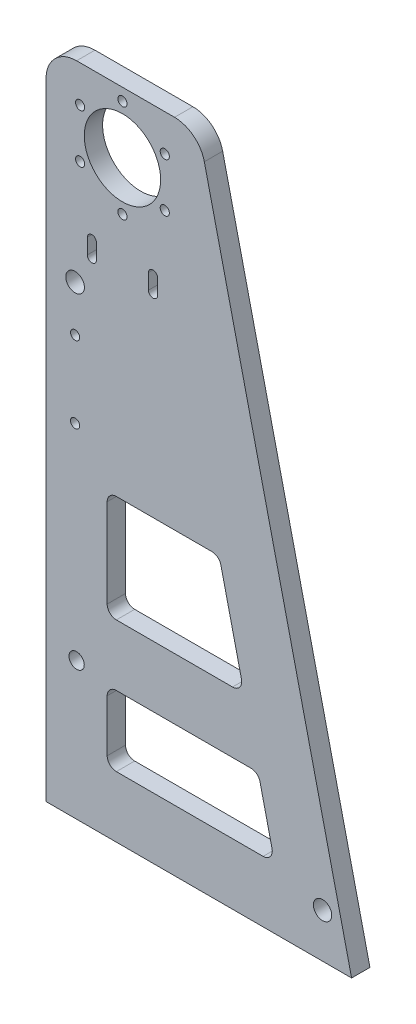
SolidWorks part; units mm, degrees
material "Policarbonato"
ref_plane "Plano frontal" through (0, 0, 0) normal (0, 0, 1) x (1, 0, 0)
ref_plane "Plano superior" through (0, 0, 0) normal (0, 1, 0) x (1, 0, 0)
ref_plane "Plano direito" through (0, 0, 0) normal (1, 0, 0) x (0, 0, -1)
sketch "Esboço1" plane through (0, 0, 0) normal (0, 0, 1) x (1, 0, 0)
  line L0 (0, 0) -> (0, 215)
  line L2 (100, 0) -> (0, 0)
  line L3 (0, 215) -> (50, 215)
  line L4 (50, 215) -> (100, 0)
  line L5 (10, 75.4302) -> (10, 15) construction
  line L6 (25, 215) -> (25, 175) construction
  line L7 (10, 15) -> (85.7122, 15) construction
  line L8 (85.7122, 15) -> (71.6586, 75.4302) construction
  line L9 (71.6586, 75.4302) -> (10, 75.4302) construction
  line L10 (20, 95) -> (20, 66)
  line L11 (23, 63) -> (61.0374, 63)
  line L12 (63.9594, 66.6795) -> (57.2152, 95.6795)
  line L13 (54.2932, 98) -> (23, 98)
  line L14 (20, 40) -> (20, 23)
  line L15 (23, 20) -> (71.0374, 20)
  line L16 (73.9594, 23.6795) -> (70.0059, 40.6795)
  line L17 (23, 43) -> (67.0839, 43)
  circle A0 centre (25, 195) radius 12.5
  circle A1 centre (25, 195) radius 16 construction
  circle A2 centre (25, 211) radius 1.5
  arc A8 (70.0059, 40.6795) -> (67.0839, 43) centre (67.0839, 40) ccw
  arc A9 (71.0374, 20) -> (73.9594, 23.6795) centre (71.0374, 23) ccw
  arc A10 (20, 23) -> (23, 20) centre (23, 23) ccw
  arc A11 (20, 40) -> (23, 43) centre (23, 40) cw
  arc A12 (57.2152, 95.6795) -> (54.2932, 98) centre (54.2932, 95) ccw
  arc A13 (61.0374, 63) -> (63.9594, 66.6795) centre (61.0374, 66) ccw
  arc A14 (20, 66) -> (23, 63) centre (23, 66) ccw
  arc A15 (20, 95) -> (23, 98) centre (23, 95) cw
  circle A16 centre (38.8564, 203) radius 1.5
  circle A17 centre (38.8564, 187) radius 1.5
  circle A18 centre (25, 179) radius 1.5
  circle A19 centre (11.1436, 187) radius 1.5
  circle A20 centre (11.1436, 203) radius 1.5
  circle A21 centre (10, 45) radius 2.5
  point P26 (22.5, 105)
  point P49 (20, 63)
  point P55 (25, 175)
  point P56 (25, 195)
  dimension "D3" = 20
  dimension "D4" = 25
  dimension "D6" = 32
  dimension "D7" = 3
  dimension "D21" = 3
  dimension "D15" = 10
  dimension "D16" = 45
  dimension "D17" = 5
  dimension "D1" = 215
  dimension "D2" = 100
  dimension "D5" = 50
  dimension "D9" = 25
  dimension "D10" = 6
  dimension "D11" = 20
  dimension "D12" = 20
  dimension "D13" = 15
  dimension "D14" = 20
  dimension "D18" = 10
  dimension "D20" = 20
  dimension "D22" = 23
  dimension "D8" = 35
extrude "Ressalto-extrusão2" add sketch "Esboço1" along normal blind 6
fillet "Filete1" radius 10 2 edges at (0, 215, 3) (50, 215, 3)
sketch "Esboço2" plane through (0, 0, 6) normal (0, 0, 1) x (1, 0, 0)
  line L0 (0, 0) -> (100, 0) construction
  line L1 (0, 205) -> (0, 0) construction
  line L2 (15, 164.21) -> (35, 164.21) construction
  line L3 (15, 161.71) -> (15, 166.71) construction
  line L4 (13.5, 161.71) -> (13.5, 166.71)
  line L5 (16.5, 161.71) -> (16.5, 166.71)
  line L6 (35, 161.71) -> (35, 166.71) construction
  line L7 (33.5, 161.71) -> (33.5, 166.71)
  line L8 (36.5, 161.71) -> (36.5, 166.71)
  circle A0 centre (9.5, 137) radius 1.5
  circle A1 centre (90.5, 14.5) radius 3
  circle A2 centre (9.5, 112) radius 1.5
  circle A3 centre (9.5, 152) radius 3.05
  circle A4 centre (15, 164.21) radius 1.5 construction
  circle A5 centre (35, 164.21) radius 1.5 construction
  arc A6 (13.5, 161.71) -> (16.5, 161.71) centre (15, 161.71) ccw
  arc A7 (16.5, 166.71) -> (13.5, 166.71) centre (15, 166.71) ccw
  arc A8 (33.5, 161.71) -> (36.5, 161.71) centre (35, 161.71) ccw
  arc A9 (36.5, 166.71) -> (33.5, 166.71) centre (35, 166.71) ccw
  point P2 (9.5, 112)
  point P3 (9.5, 137)
  point P18 (25, 195)
  point P20 (25, 164.21)
  point P22 (15, 164.21)
  point P30 (35, 164.21)
  dimension "D4" = 3
  dimension "D7" = 6
  dimension "D8" = 6.1
  dimension "D10" = 3
  dimension "D1" = 112
  dimension "D2" = 25
  dimension "D3" = 9.5
  dimension "D5" = 14.5
  dimension "D6" = 9.5
  dimension "D9" = 15
  dimension "D11" = 20
  dimension "D12" = 30.79
  dimension "D13" = 5
extrude "Corte-extrusão1" cut sketch "Esboço2" against normal through all
